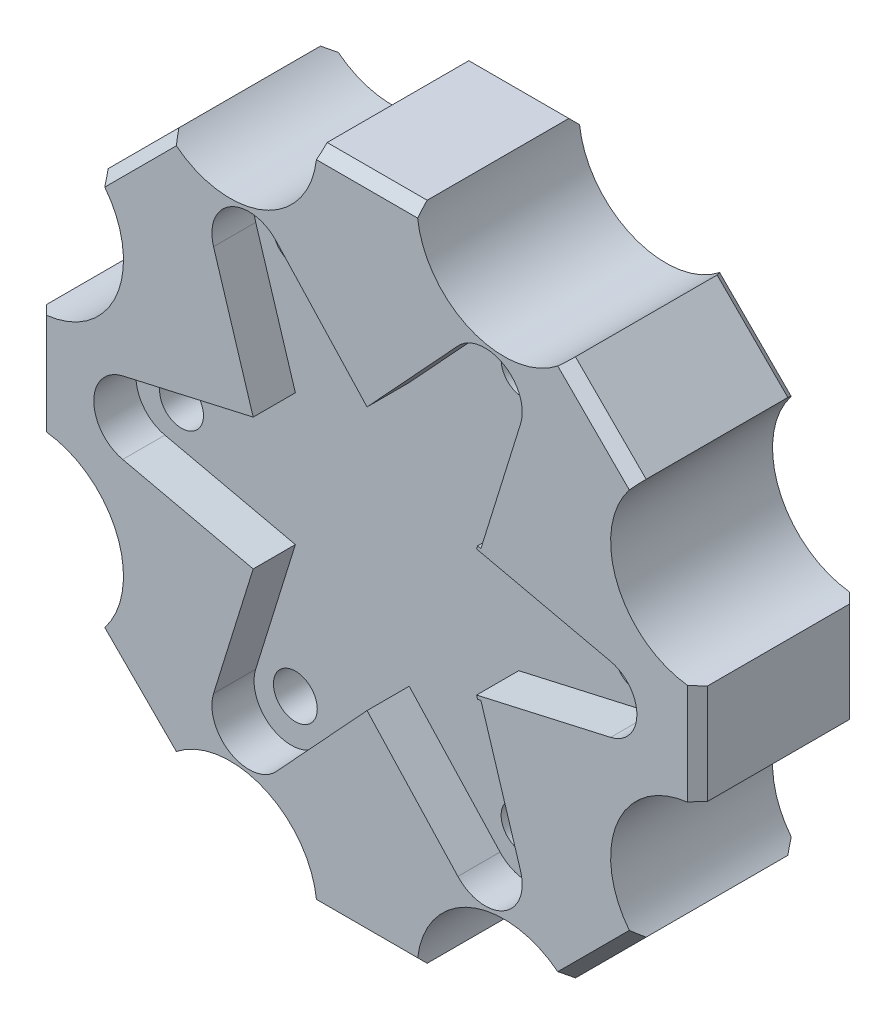
SolidWorks part; units mm, degrees
ref_plane "Front Plane" through (0, 0, 0) normal (0, 0, 1) x (1, 0, 0)
ref_plane "Top Plane" through (0, 0, 0) normal (0, 1, 0) x (1, 0, 0)
ref_plane "Right Plane" through (0, 0, 0) normal (1, 0, 0) x (0, 0, -1)
sketch "Sketch1" plane through (0, 0, 0) normal (0, 0, 1) x (1, 0, 0)
  line L1 (-8.115, -19.5913) -> (8.115, -19.5913)
  line L2 (8.115, -19.5913) -> (19.5913, -8.115)
  line L3 (19.5913, -8.115) -> (19.5913, 8.115)
  line L4 (19.5913, 8.115) -> (8.115, 19.5913)
  line L5 (8.115, 19.5913) -> (-8.115, 19.5913)
  line L6 (-8.115, 19.5913) -> (-19.5913, 8.115)
  line L7 (-19.5913, 8.115) -> (-19.5913, -8.115)
  line L8 (-19.5913, -8.115) -> (-8.115, -19.5913)
  circle A0 centre (0, 0) radius 19.5913 construction
  circle A1 centre (-8.115, 19.5913) radius 4.95 construction
  circle A2 centre (8.115, 19.5913) radius 4.95 construction
  arc A3 (-11.7566, 15.9497) -> (-2.965, 19.5913) centre (-8.115, 19.5913) ccw
  arc A4 (2.965, 19.5913) -> (11.7566, 15.9497) centre (8.115, 19.5913) ccw
  arc A5 (15.9497, 11.7566) -> (19.5913, 2.965) centre (19.5913, 8.115) ccw
  circle A6 centre (-8.115, 19.5913) radius 5.15 construction
  circle A7 centre (8.115, 19.5913) radius 5.15 construction
  arc A8 (19.5913, -2.965) -> (15.9497, -11.7566) centre (19.5913, -8.115) ccw
  arc A9 (11.7566, -15.9497) -> (2.965, -19.5913) centre (8.115, -19.5913) ccw
  arc A10 (-2.965, -19.5913) -> (-11.7566, -15.9497) centre (-8.115, -19.5913) ccw
  arc A11 (-15.9497, -11.7566) -> (-19.5913, -2.965) centre (-19.5913, -8.115) ccw
  arc A12 (-19.5913, 2.965) -> (-15.9497, 11.7566) centre (-19.5913, 8.115) ccw
  point P15 (13.265, 19.5913)
  point P18 (-2.965, 19.5913)
  point P44 (0, 0)
  dimension "D2" = 9.9
  dimension "D1" = 16.23
  dimension "D3" = 0.2
  dimension "D4" = 4
extrude "Boss-Extrude1" add sketch "Sketch1" along normal blind 9.6 contours A12 L7 A11 L8 A10 L1 A9 L2 A8 L3 A5 L4 A4 L5 A3 L6 region at (0, 0, 0)
chamfer "Chamfer2" distance 0.6 angle 45 16 edges at (0, -19.5913, 0) (-13.8532, -13.8532, 0) (-19.5913, 0, 0) (-13.8532, 13.8532, 0) (0, 19.5913, 0) (13.8532, 13.8532, 0) (19.5913, 0, 0) (13.8532, -13.8532, 0) (-13.8532, 13.8532, 9.6) (0, 19.5913, 9.6) (13.8532, 13.8532, 9.6) (19.5913, 0, 9.6) (13.8532, -13.8532, 9.6) (0, -19.5913, 9.6) (-13.8532, -13.8532, 9.6) (-19.5913, 0, 9.6)
sketch "Sketch3" plane through (0, 0, 9.6) normal (0, 0, 1) x (1, 0, 0)
  line L0 (0, 0) -> (-2.5, 0) construction
  line L1 (-2.5, 0) -> (-5.5, 0) construction
  line L2 (-2, -1.5) -> (-5.5, -1.5)
  line L3 (-5.5, -1.5) -> (-5.5, 1.5)
  line L4 (-5.5, 1.5) -> (-2, 1.5)
  line L5 (0, 2.5) -> (0, -2.5) construction
  line L6 (5.5, 1.5) -> (2, 1.5)
  line L7 (5.5, -1.5) -> (5.5, 1.5)
  line L8 (2, -1.5) -> (5.5, -1.5)
  arc A0 (-2, -1.5) -> (2, -1.5) centre (0, 0) ccw
  arc A1 (-2.5, 0) -> (-2, -1.5) centre (0, 0) ccw construction
  arc A2 (-2, 1.5) -> (-2.5, 0) centre (0, 0) ccw construction
  arc A3 (2, 1.5) -> (-2, 1.5) centre (0, 0) ccw
  arc A4 (2, -1.5) -> (2, 1.5) centre (0, 0) ccw construction
  point P1 (0, 0)
  point P13 (0, 0)
  dimension "D3" = 5
  dimension "D1" = 3
  dimension "D2" = 3
extrude "Cut-Extrude1" [suppressed] cut sketch "Sketch3" against normal through all
sketch "Sketch4" plane through (0, 0, 9.6) normal (0, 0, 1) x (1, 0, 0)
  line L0 (14.4417, 1.9506) -> (6.4952, 3.75)
  line L1 (14.4417, -1.9506) -> (6.4952, -3.75)
  line L2 (6.4952, -3.75) -> (6.4952, 3.75) construction
  line L3 (14, 0) -> (7.5, 0) construction
  line L4 (5.5316, -13.4822) -> (0, -7.5)
  line L5 (8.9101, -11.5316) -> (6.4952, -3.75)
  line L6 (-8.9101, -11.5316) -> (-6.4952, -3.75)
  line L7 (-5.5316, -13.4822) -> (0, -7.5)
  line L8 (-14.4417, 1.9506) -> (-6.4952, 3.75)
  line L9 (-14.4417, -1.9506) -> (-6.4952, -3.75)
  line L10 (-5.5316, 13.4822) -> (0, 7.5)
  line L11 (-8.9101, 11.5316) -> (-6.4952, 3.75)
  line L12 (8.9101, 11.5316) -> (6.4952, 3.75)
  line L13 (5.5316, 13.4822) -> (0, 7.5)
  line L14 (9.1011, -11.4723) -> (6.6862, -3.6907)
  line L15 (5.3847, -13.618) -> (0, -7.7946)
  line L16 (-5.3847, -13.618) -> (0, -7.7946)
  line L17 (-9.1011, -11.4723) -> (-6.7503, -3.8973)
  line L18 (-14.4859, -2.1457) -> (-6.7503, -3.8973)
  line L19 (-14.4859, 2.1457) -> (-6.7503, 3.8973)
  line L20 (-9.1011, 11.4723) -> (-6.7503, 3.8973)
  line L21 (-5.3847, 13.618) -> (0, 7.7946)
  line L22 (5.3847, 13.618) -> (0, 7.7946)
  line L23 (9.1011, 11.4723) -> (6.6862, 3.6907)
  line L24 (14.4859, 2.1457) -> (6.5394, 3.9451)
  line L25 (14.4859, -2.1457) -> (6.5394, -3.9451)
  arc A0 (14.4417, -1.9506) -> (14.4417, 1.9506) centre (14, 0) ccw
  circle A1 centre (0, 0) radius 7.5 construction
  arc A2 (5.5316, -13.4822) -> (8.9101, -11.5316) centre (7, -12.1244) ccw
  arc A3 (-8.9101, -11.5316) -> (-5.5316, -13.4822) centre (-7, -12.1244) ccw
  arc A4 (-14.4417, 1.9506) -> (-14.4417, -1.9506) centre (-14, 0) ccw
  arc A5 (-5.5316, 13.4822) -> (-8.9101, 11.5316) centre (-7, 12.1244) ccw
  arc A6 (8.9101, 11.5316) -> (5.5316, 13.4822) centre (7, 12.1244) ccw
  arc A7 (5.3847, -13.618) -> (9.1011, -11.4723) centre (7, -12.1244) ccw
  arc A8 (-9.1011, -11.4723) -> (-5.3847, -13.618) centre (-7, -12.1244) ccw
  arc A9 (-14.4859, 2.1457) -> (-14.4859, -2.1457) centre (-14, 0) ccw
  arc A10 (-5.3847, 13.618) -> (-9.1011, 11.4723) centre (-7, 12.1244) ccw
  arc A11 (9.1011, 11.4723) -> (5.3847, 13.618) centre (7, 12.1244) ccw
  arc A12 (14.4859, -2.1457) -> (14.4859, 2.1457) centre (14, 0) ccw
  point P3 (16, 0)
  point P37 (0, 0)
  dimension "D2" = 2
  dimension "D3" = 15
  dimension "D1" = 16
  dimension "D4" = 7.5
  dimension "D6" = 0.2
  dimension "D5" = 6
extrude "Cut-Extrude2" cut sketch "Sketch4" against normal blind 2.5 contours L12 A6 L13 L10 A5 L11 L8 A4 L9 L6 A3 L7 L4 A2 L5 L1 A0 L0 | L23 A11 L22 L21 A10 L20 L19 A9 L18 L17 A8 L16 L15 A7 L14 L25 L5 A2 L4 L7 A3 L6 L9 A4 L8 L11 A5 L10 L13 A6 L12 L24 region at (0, 0, 9.6) region at (6.737, 4.2929, 9.6)
hole_wizard "M2 Clearance Hole1" positions "Sketch7" profile "Sketch6" hole size "M2" standard "ANSI Metric" end condition through all
sketch "Sketch7" plane through (0, 0, 7.1) normal (0, 0, 1) x (1, 0, 0)
  line L0 (0, 0) -> (13.5, 0) construction
  point P0 (13.5, 0)
  point P10 (6.75, -11.6913)
  point P11 (-6.75, -11.6913)
  point P12 (-13.5, 0)
  point P13 (-6.75, 11.6913)
  point P14 (6.75, 11.6913)
  point P16 (0, 0)
  dimension "D1" = 13.5
  dimension "D2" = 6
sketch "Sketch6" plane through (13.5, 0, 7.1) normal (1, 0, 0) x (0, -1, 0)
  line L0 (0, 0) -> (0, 7.1)
  line L1 (0, 7.1) -> (1.3, 7.1)
  line L2 (1.3, 7.1) -> (1.3, 0)
  line L5 (1.3, 0) -> (0, 0)
  line L11 (0, -6.35) -> (0, 107.95) construction
  dimension "Thru Hole Dia." = 2.6
  dimension "Thru Hole Depth" = 7.1
extrude "Cut-Extrude3" cut sketch "Sketch3<2>" along normal blind 5.5 from surface starting at face at (14.8, 0, 0)
sketch "Sketch3<2>" plane through (0, 0, 9.6) normal (0, 0, 1) x (1, 0, 0) same geometry as "Sketch3"
chamfer "Chamfer3" distance 1.5 angle 45 8 edges at (3.75, -1.5, 5.5) (5.5, 0, 5.5) (3.75, 1.5, 5.5) (0, 2.5, 5.5) (-3.75, 1.5, 5.5) (-5.5, 0, 5.5) (-3.75, -1.5, 5.5) (0, -2.5, 5.5)
